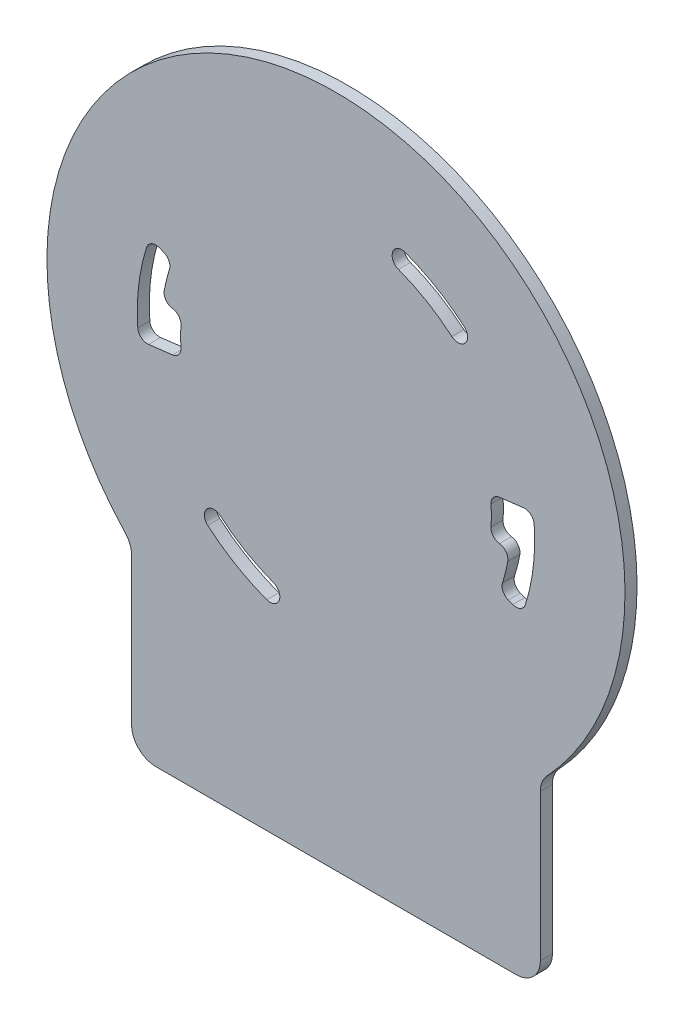
SolidWorks part; units mm, degrees
ref_plane "Front Plane" through (0, 0, 0) normal (0, 0, 1) x (1, 0, 0)
ref_plane "Top Plane" through (0, 0, 0) normal (0, 1, 0) x (1, 0, 0)
ref_plane "Right Plane" through (0, 0, 0) normal (1, 0, 0) x (0, 0, -1)
sketch "Sketch1" plane through (0, 0, 0) normal (0, 0, 1) x (1, 0, 0)
  line L0 (0, -38.4823) -> (0, 38.4823) construction
  line L1 (-18.1008, 0) -> (18.1008, 0) construction
  line L2 (15.4551, -5.7784) -> (0, 0) construction
  line L3 (16.377, 2.0108) -> (0, 0) construction
  line L4 (16.377, 2.0108) -> (12.8038, 1.5721)
  line L5 (12.8038, -1.5721) -> (0, 0) construction
  line L6 (12.8038, -1.5721) -> (14.3919, -1.7671)
  line L7 (15.4551, -5.7784) -> (13.5817, -5.078)
  line L8 (-16.9706, -16.9706) -> (0, 0) construction
  line L9 (16.9706, -16.9706) -> (0, 0) construction
  line L10 (-16.9706, -16.9706) -> (-16.9706, -29.9706)
  line L11 (16.9706, -16.9706) -> (16.9706, -29.9706)
  line L12 (-14.9706, -31.9706) -> (14.9706, -31.9706)
  line L16 (-16.377, -2.0108) -> (-12.8038, -1.5721)
  line L17 (-15.4551, 5.7784) -> (-13.5817, 5.078)
  line L18 (-12.8038, 1.5721) -> (-14.3919, 1.7671)
  line L19 (-9.6118, -11.254) -> (0, 0) construction
  line L20 (-5.1831, -13.8627) -> (0, 0) construction
  line L21 (5.4632, 14.6121) -> (0, 0) construction
  line L22 (10.1314, 11.8623) -> (0, 0) construction
  arc A0 (15.4551, -5.7784) -> (16.377, 2.0108) centre (0, 0) ccw
  arc A1 (12.8038, 1.5721) -> (12.8038, -1.5721) centre (0, 0) cw
  arc A2 (13.5817, -5.078) -> (14.3919, -1.7671) centre (0, 0) ccw
  arc A4 (16.9706, -16.9706) -> (-16.9706, -16.9706) centre (0, 0) ccw
  arc A5 (-16.9706, -29.9706) -> (-14.9706, -31.9706) centre (-14.9706, -29.9706) ccw
  arc A6 (14.9706, -31.9706) -> (16.9706, -29.9706) centre (14.9706, -29.9706) ccw
  arc A7 (-12.8038, 1.5721) -> (-12.8038, -1.5721) centre (0, 0) ccw
  arc A10 (-15.4551, 5.7784) -> (-16.377, -2.0108) centre (0, 0) ccw
  arc A11 (-13.5817, 5.078) -> (-14.3919, 1.7671) centre (0, 0) ccw
  arc A12 (-9.6118, -11.254) -> (-5.1831, -13.8627) centre (0, 0) ccw
  arc A13 (-10.6509, -12.4707) -> (-5.7434, -15.3614) centre (0, 0) ccw
  arc A14 (-9.6118, -11.254) -> (-10.6509, -12.4707) centre (-10.1314, -11.8623) ccw
  arc A15 (-5.7434, -15.3614) -> (-5.1831, -13.8627) centre (-5.4632, -14.6121) ccw
  arc A16 (5.7434, 15.3614) -> (5.1831, 13.8627) centre (5.4632, 14.6121) ccw
  arc A17 (9.6118, 11.254) -> (5.1831, 13.8627) centre (0, 0) ccw
  arc A18 (9.6118, 11.254) -> (10.6509, 12.4707) centre (10.1314, 11.8623) ccw
  arc A19 (10.6509, 12.4707) -> (5.7434, 15.3614) centre (0, 0) ccw
  point P7 (0, 0)
  point P10 (0, 0)
  point P43 (0, 0)
  dimension "D1" = 16.5
  dimension "D6" = 24
  dimension "D12" = 2
  dimension "D13" = 16.5
  dimension "D14" = 14.5
  dimension "D15" = 14.8
  dimension "D18" = 16.4
  dimension "D2" = 20.5
  dimension "D3" = 7
  dimension "D4" = 3.6
  dimension "D5" = 7
  dimension "D7" = 2
  dimension "D8" = 45
  dimension "D9" = 45
  dimension "D10" = 13
  dimension "D11" = 13
  dimension "D16" = 42.5
  dimension "D17" = 20
  dimension "D20" = 42.5
  dimension "D19" = 2
extrude "Outline" add sketch "Sketch1" along normal blind 1
fillet "Fillets" radius 0.8 12 edges at (16.377, 2.0108, 0.5) (12.8038, 1.5721, 0.5) (13.5817, -5.078, 0.5) (15.4551, -5.7784, 0.5) (14.3919, -1.7671, 0.5) (12.8038, -1.5721, 0.5) (-12.8038, -1.5721, 0.5) (-16.377, -2.0108, 0.5) (-15.4551, 5.7784, 0.5) (-13.5817, 5.078, 0.5) (-12.8038, 1.5721, 0.5) (-14.3919, 1.7671, 0.5)
fillet "Fillet2" radius 2 2 edges at (16.9706, -16.9706, 0.5) (-16.9706, -16.9706, 0.5)
sketch "Sketch2" plane through (0, 0, 1) normal (0, 0, 1) x (1, 0, 0)
  line L0 (-14.3115, 5.3508) -> (-14.6866, 5.4911) construction
  line L1 (-16.9706, -17.7797) -> (-16.9706, -29.9706) construction
  line L2 (-14.9706, -31.9706) -> (14.9706, -31.9706) construction
  line L3 (16.9706, -29.9706) -> (16.9706, -17.7797) construction
  line L4 (14.3115, -5.3508) -> (14.6866, -5.4911) construction
  line L5 (15.5627, 1.9109) -> (13.5747, 1.6668) construction
  line L6 (-15.5627, -1.9109) -> (-13.5747, -1.6668) construction
  line L7 (-16.9706, -17.7797) -> (-16.9706, -29.9706)
  line L8 (-14.9706, -31.9706) -> (14.9706, -31.9706)
  line L9 (16.9706, -29.9706) -> (16.9706, -17.7797)
  line L10 (14.3115, -5.3508) -> (14.6866, -5.4911)
  line L11 (15.5627, 1.9109) -> (13.5747, 1.6668)
  line L12 (-15.5627, -1.9109) -> (-13.5747, -1.6668)
  line L13 (-14.3115, 5.3508) -> (-14.6866, 5.4911)
  arc A0 (-14.6866, 5.4911) -> (-15.7295, 4.9834) centre (-14.9668, 4.7418) ccw construction
  arc A1 (-16.9706, -17.7797) -> (-17.5113, -16.412) centre (-18.9706, -17.7797) ccw construction
  arc A2 (-16.9706, -29.9706) -> (-14.9706, -31.9706) centre (-14.9706, -29.9706) ccw construction
  arc A3 (14.9706, -31.9706) -> (16.9706, -29.9706) centre (14.9706, -29.9706) ccw construction
  arc A4 (17.5113, -16.412) -> (16.9706, -17.7797) centre (18.9706, -17.7797) ccw construction
  arc A5 (17.5113, -16.412) -> (-17.5113, -16.412) centre (0, 0) ccw construction
  arc A6 (5.7434, 15.3614) -> (5.1831, 13.8627) centre (5.4632, 14.6121) ccw construction
  arc A7 (10.6509, 12.4707) -> (5.7434, 15.3614) centre (0, 0) ccw construction
  arc A8 (9.6118, 11.254) -> (5.1831, 13.8627) centre (0, 0) ccw construction
  arc A9 (9.6118, 11.254) -> (10.6509, 12.4707) centre (10.1314, 11.8623) ccw construction
  arc A10 (14.6866, -5.4911) -> (15.7295, -4.9834) centre (14.9668, -4.7418) ccw construction
  arc A11 (13.8287, -4.3609) -> (14.3115, -5.3508) centre (14.5916, -4.6015) ccw construction
  arc A12 (15.7295, -4.9834) -> (16.4582, 1.1737) centre (0, 0) ccw construction
  arc A13 (16.4582, 1.1737) -> (15.5627, 1.9109) centre (15.6602, 1.1168) ccw construction
  arc A14 (13.5747, 1.6668) -> (12.8738, 0.8218) centre (13.6722, 0.8727) ccw construction
  arc A15 (12.8738, -0.8218) -> (12.8738, 0.8218) centre (0, 0) ccw construction
  arc A16 (12.8738, -0.8218) -> (13.5747, -1.6668) centre (13.6722, -0.8727) ccw construction
  arc A17 (14.2642, -2.6045) -> (13.5747, -1.6668) centre (13.4772, -2.4608) ccw construction
  arc A18 (13.8287, -4.3609) -> (14.2642, -2.6045) centre (0, 0) ccw construction
  arc A19 (-9.6118, -11.254) -> (-10.6509, -12.4707) centre (-10.1314, -11.8623) ccw construction
  arc A20 (-9.6118, -11.254) -> (-5.1831, -13.8627) centre (0, 0) ccw construction
  arc A21 (-5.7434, -15.3614) -> (-5.1831, -13.8627) centre (-5.4632, -14.6121) ccw construction
  arc A22 (-10.6509, -12.4707) -> (-5.7434, -15.3614) centre (0, 0) ccw construction
  arc A23 (-14.2642, 2.6045) -> (-13.5747, 1.6668) centre (-13.4772, 2.4608) ccw construction
  arc A24 (-12.8738, 0.8218) -> (-13.5747, 1.6668) centre (-13.6722, 0.8727) ccw construction
  arc A25 (-12.8738, 0.8218) -> (-12.8738, -0.8218) centre (0, 0) ccw construction
  arc A26 (-13.5747, -1.6668) -> (-12.8738, -0.8218) centre (-13.6722, -0.8727) ccw construction
  arc A27 (-16.4582, -1.1737) -> (-15.5627, -1.9109) centre (-15.6602, -1.1168) ccw construction
  arc A28 (-15.7295, 4.9834) -> (-16.4582, -1.1737) centre (0, 0) ccw construction
  arc A29 (-13.8287, 4.3609) -> (-14.2642, 2.6045) centre (0, 0) ccw construction
  arc A30 (-13.8287, 4.3609) -> (-14.3115, 5.3508) centre (-14.5916, 4.6015) ccw construction
  arc A31 (-16.9706, -17.7797) -> (-17.5113, -16.412) centre (-18.9706, -17.7797) ccw
  arc A32 (-16.9706, -29.9706) -> (-14.9706, -31.9706) centre (-14.9706, -29.9706) ccw
  arc A33 (14.9706, -31.9706) -> (16.9706, -29.9706) centre (14.9706, -29.9706) ccw
  arc A34 (17.5113, -16.412) -> (16.9706, -17.7797) centre (18.9706, -17.7797) ccw
  arc A35 (17.5113, -16.412) -> (-17.5113, -16.412) centre (0, 0) ccw
  arc A36 (5.7434, 15.3614) -> (5.1831, 13.8627) centre (5.4632, 14.6121) ccw
  arc A37 (10.6509, 12.4707) -> (5.7434, 15.3614) centre (0, 0) ccw
  arc A38 (9.6118, 11.254) -> (5.1831, 13.8627) centre (0, 0) ccw
  arc A39 (9.6118, 11.254) -> (10.6509, 12.4707) centre (10.1314, 11.8623) ccw
  arc A40 (14.6866, -5.4911) -> (15.7295, -4.9834) centre (14.9668, -4.7418) ccw
  arc A41 (13.8287, -4.3609) -> (14.3115, -5.3508) centre (14.5916, -4.6015) ccw
  arc A42 (15.7295, -4.9834) -> (16.4582, 1.1737) centre (0, 0) ccw
  arc A43 (16.4582, 1.1737) -> (15.5627, 1.9109) centre (15.6602, 1.1168) ccw
  arc A44 (13.5747, 1.6668) -> (12.8738, 0.8218) centre (13.6722, 0.8727) ccw
  arc A45 (12.8738, -0.8218) -> (12.8738, 0.8218) centre (0, 0) ccw
  arc A46 (12.8738, -0.8218) -> (13.5747, -1.6668) centre (13.6722, -0.8727) ccw
  arc A47 (14.2642, -2.6045) -> (13.5747, -1.6668) centre (13.4772, -2.4608) ccw
  arc A48 (13.8287, -4.3609) -> (14.2642, -2.6045) centre (0, 0) ccw
  arc A49 (-9.6118, -11.254) -> (-10.6509, -12.4707) centre (-10.1314, -11.8623) ccw
  arc A50 (-9.6118, -11.254) -> (-5.1831, -13.8627) centre (0, 0) ccw
  arc A51 (-5.7434, -15.3614) -> (-5.1831, -13.8627) centre (-5.4632, -14.6121) ccw
  arc A52 (-10.6509, -12.4707) -> (-5.7434, -15.3614) centre (0, 0) ccw
  arc A53 (-14.2642, 2.6045) -> (-13.5747, 1.6668) centre (-13.4772, 2.4608) ccw
  arc A54 (-12.8738, 0.8218) -> (-13.5747, 1.6668) centre (-13.6722, 0.8727) ccw
  arc A55 (-12.8738, 0.8218) -> (-12.8738, -0.8218) centre (0, 0) ccw
  arc A56 (-13.5747, -1.6668) -> (-12.8738, -0.8218) centre (-13.6722, -0.8727) ccw
  arc A57 (-16.4582, -1.1737) -> (-15.5627, -1.9109) centre (-15.6602, -1.1168) ccw
  arc A58 (-15.7295, 4.9834) -> (-16.4582, -1.1737) centre (0, 0) ccw
  arc A59 (-13.8287, 4.3609) -> (-14.2642, 2.6045) centre (0, 0) ccw
  arc A60 (-13.8287, 4.3609) -> (-14.3115, 5.3508) centre (-14.5916, 4.6015) ccw
  arc A61 (-14.6866, 5.4911) -> (-15.7295, 4.9834) centre (-14.9668, 4.7418) ccw
